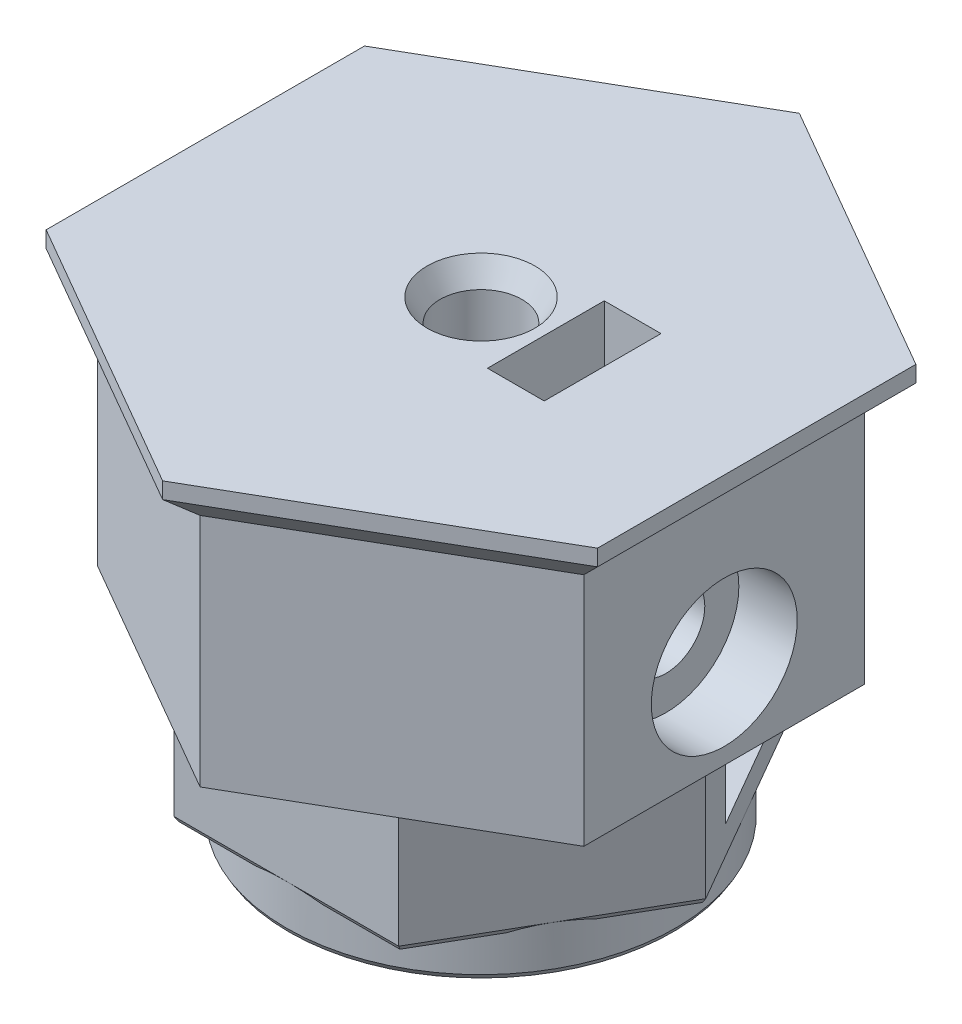
SolidWorks part; units mm, degrees
ref_plane "Ebene vorne" through (0, 0, 0) normal (0, 0, 1) x (1, 0, 0)
ref_plane "Ebene oben" through (0, 0, 0) normal (0, 1, 0) x (1, 0, 0)
ref_plane "Ebene rechts" through (0, 0, 0) normal (1, 0, 0) x (0, 0, -1)
sketch "Skizze1" plane through (0, 0, 0) normal (0, 1, 0) x (1, 0, 0)
  line L1 (15, 8.6603) -> (0, 17.3205)
  line L2 (0, 17.3205) -> (-15, 8.6603)
  line L3 (-15, 8.6603) -> (-15, -8.6603)
  line L4 (-15, -8.6603) -> (0, -17.3205)
  line L5 (0, -17.3205) -> (15, -8.6603)
  line L6 (15, -8.6603) -> (15, 8.6603)
  circle A0 centre (0, 0) radius 15 construction
  circle A1 centre (0, 0) radius 2.525
  dimension "D1" = 5.05
  dimension "D2" = 30
extrude "Aufsatz-Linear austragen1" add sketch "Skizze1" along normal blind 28
sketch "Skizze2" plane through (0, 28, 0) normal (0, 1, 0) x (1, 0, 0)
  line L1 (4, 3.6) -> (7.5, 3.6)
  line L2 (4, 3.6) -> (4, -3.6)
  line L3 (4, -3.6) -> (7.5, -3.6)
  line L4 (7.5, 3.6) -> (7.5, -3.6)
  dimension "D1" = 7.2
  dimension "D2" = 3.6
  dimension "D3" = 3.5
  dimension "D4" = 4
extrude "Schnitt-Linear austragen1" cut sketch "Skizze2" against normal blind 16.2
sketch "Skizze4" plane through (15, 0, 0) normal (1, 0, 0) x (0, 0, -1)
  line L0 (-8.6603, 28) -> (8.6603, 28) construction
  circle A0 centre (0, 16) radius 2.4
  dimension "D1" = 12
extrude "Schnitt-Linear austragen2" cut sketch "Skizze4" against normal blind 16 contours A0
sketch "Skizze6" plane through (0, 28, 0) normal (0, 1, 0) x (1, 0, 0)
  line L1 (0, -19.6299) -> (17, -9.815)
  line L2 (17, -9.815) -> (17, 9.815)
  line L3 (17, 9.815) -> (0, 19.6299)
  line L4 (0, 19.6299) -> (-17, 9.815)
  line L5 (-17, 9.815) -> (-17, -9.815)
  line L6 (-17, -9.815) -> (0, -19.6299)
  circle A1 centre (0, 0) radius 14.009
  circle A2 centre (0, 0) radius 17 construction
extrude "Aufsatz-Linear austragen3" add sketch "Skizze6" against normal blind 3
sketch "Skizze7" plane through (0, 0, 0) normal (0, -1, 0) x (1, 0, 0)
  line L1 (-6.9282, 12) -> (-13.8564, 0)
  line L2 (-13.8564, 0) -> (-6.9282, -12)
  line L3 (-6.9282, -12) -> (6.9282, -12)
  line L4 (6.9282, -12) -> (13.8564, 0)
  line L5 (13.8564, 0) -> (6.9282, 12)
  line L6 (6.9282, 12) -> (-6.9282, 12)
  circle A0 centre (0, 0) radius 12 construction
  circle A1 centre (0, 0) radius 20
extrude "Schnitt-Linear austragen4" cut sketch "Skizze7" against normal blind 10.5
chamfer "Fase1" distance 0.8 angle 60 1 edges at (0, 28, 2.525) first distance on face at (0, 28, 0)
sketch "Skizze9" plane through (10.3923, 0, -6) normal (0.866, 0, -0.5) x (-0.5, 0, -0.866)
  line L0 (6.9282, 10.5) -> (-6.9282, 10.5) construction
  line L1 (-3.6, 8) -> (3.6, 8)
  line L2 (-3.6, 8) -> (-3.6, 4.5)
  line L3 (-3.6, 4.5) -> (3.6, 4.5)
  line L4 (3.6, 8) -> (3.6, 4.5)
  dimension "D1" = 7.2
  dimension "D2" = 3.5
  dimension "D3" = 2.5
extrude "Schnitt-Linear austragen5" cut sketch "Skizze9" against normal blind 16
sketch "Skizze10" plane through (0, 0, 0) normal (0, -1, 0) x (1, 0, 0)
  circle A0 centre (0, 0) radius 8.5
extrude "Schnitt-Linear austragen6" cut sketch "Skizze10" against normal blind 3
chamfer "Fase2" distance 2 angle 45 6 edges at (8.5, 25, 14.7224) (17, 25, 0) (8.5, 25, -14.7224) (-8.5, 25, -14.7224) (-17, 25, 0) (-8.5, 25, 14.7224)
sketch "Skizze11" plane through (15, 0, 0) normal (1, 0, 0) x (0, 0, -1)
  circle A0 centre (0, 16) radius 4.5
  dimension "D1" = 9
extrude "Schnitt-Linear austragen7" cut sketch "Skizze11" against normal blind 3.6 contours A0
sketch "Skizze12" plane through (0, 0, 0) normal (0, -1, 0) x (1, 0, 0)
  circle A0 centre (0, 0) radius 12
  circle A1 centre (0, 0) radius 14.3384
extrude "Schnitt-Linear austragen8" cut sketch "Skizze12" against normal blind 2.5 contours A0 | A1
chamfer "Fase3" distance 0.3 angle 30 1 edges at (0, 0, -12) first distance on face at (0, 0, -12)
chamfer "Fase4" distance 0.3 angle 30 12 edges at (-8.6603, 2.5, -9) (-8.6603, 2.5, 9) (-12.1244, 2.5, -3) (-12.1244, 2.5, 3) (-3.4641, 2.5, -12) (3.4641, 2.5, -12) (8.6603, 2.5, -9) (12.1244, 2.5, -3) (12.1244, 2.5, 3) (8.6603, 2.5, 9) (3.4641, 2.5, 12) (-3.4641, 2.5, 12) first distance on face at (-10.3923, 5.7, -6) first distance on face at (-10.3923, 5.7, 6) first distance on face at (0, 5.7, -12) first distance on face at (10.3923, 6.25, -6) first distance on face at (10.3923, 5.7, 6) first distance on face at (0, 5.7, 12)
